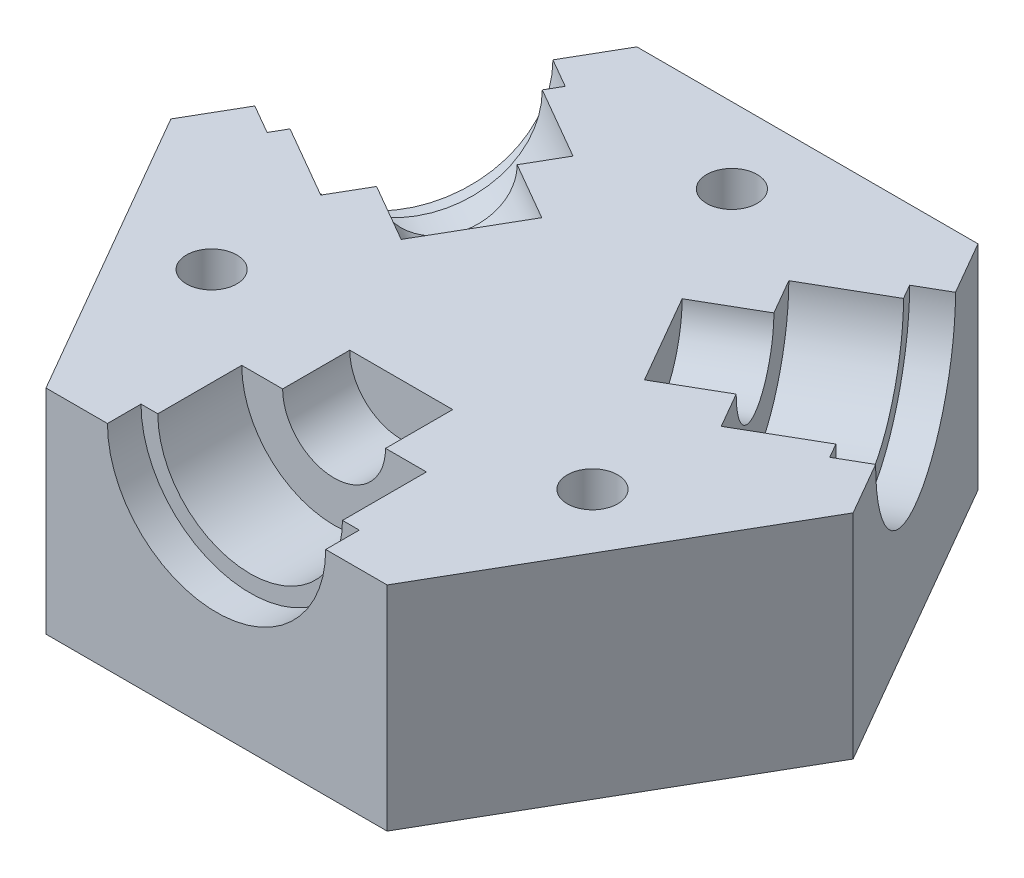
SolidWorks part; units mm, degrees
ref_plane "Front Plane" through (0, 0, 0) normal (0, 0, 1) x (1, 0, 0)
ref_plane "Top Plane" through (0, 0, 0) normal (0, 1, 0) x (1, 0, 0)
ref_plane "Right Plane" through (0, 0, 0) normal (1, 0, 0) x (0, 0, -1)
sketch "Sketch1" plane through (0, 0, 0) normal (0, 1, 0) x (1, 0, 0)
  line L1 (10.16, -17.5976) -> (20.32, 0)
  line L2 (20.32, 0) -> (10.16, 17.5976)
  line L3 (10.16, 17.5976) -> (-10.16, 17.5976)
  line L4 (-10.16, 17.5976) -> (-20.32, 0)
  line L5 (-20.32, 0) -> (-10.16, -17.5976)
  line L6 (-10.16, -17.5976) -> (10.16, -17.5976)
  circle A0 centre (0, 0) radius 17.5976 construction
  dimension "D1" = 20.32
extrude "Boss-Extrude1" add sketch "Sketch1" along normal blind 12.7 contours L4 L5 L6 L1 L2 L3
sketch "Sketch5" plane through (0, 12.7, 0) normal (0, 1, 0) x (1, 0, 0)
  line L14 (0, -17.5976) -> (0, -6.5976)
  line L15 (-10.16, -17.5976) -> (10.16, -17.5976) construction
  line L16 (0, -6.5976) -> (-3.0653, -6.5976)
  line L17 (-3.0653, -6.5976) -> (-3.0653, -10.5976)
  line L18 (-3.0653, -10.5976) -> (-5.5, -10.5976)
  line L19 (-5.5, -10.5976) -> (-5.5, -15.5976)
  line L20 (-5.5, -15.5976) -> (-6.5, -15.5976)
  line L21 (-6.5, -15.5976) -> (-6.5, -17.5976)
  line L22 (-6.5, -17.5976) -> (0, -17.5976)
  dimension "D1" = 6.5
  dimension "D2" = 5.5
  dimension "D3" = 2
  dimension "D4" = 5
  dimension "D5" = 4
  dimension "D6" = 3.0653
revolve "Cut-Revolve1" cut sketch "Sketch5" angle 360 about L14
ref_axis "Axis1" through (0, -0.635, 0) along (0, 1, 0)
pattern_circular "CirPattern1" count 3 over 360 about axis through (0, -0.635, 0) along (0, 1, 0) of "Cut-Revolve1"
sketch "Sketch7" plane through (0, 12.7, 0) normal (0, 1, 0) x (1, 0, 0)
  line L0 (10.16, 17.5976) -> (-10.16, 17.5976) construction
  line L1 (-20.32, 0) -> (-10.16, -17.5976) construction
  line L2 (10.16, -17.5976) -> (20.32, 0) construction
  circle A0 centre (0, 13.0976) radius 1.5
  circle A1 centre (11.3429, -6.5488) radius 1.5
  circle A2 centre (-11.3429, -6.5488) radius 1.5
  point P11 (0, 0)
  dimension "D1" = 3
  dimension "D2" = 3
  dimension "D4" = 3
  dimension "D5" = 3
  dimension "D3" = 3
extrude "Cut-Extrude2" cut sketch "Sketch7" against normal blind 6.35
